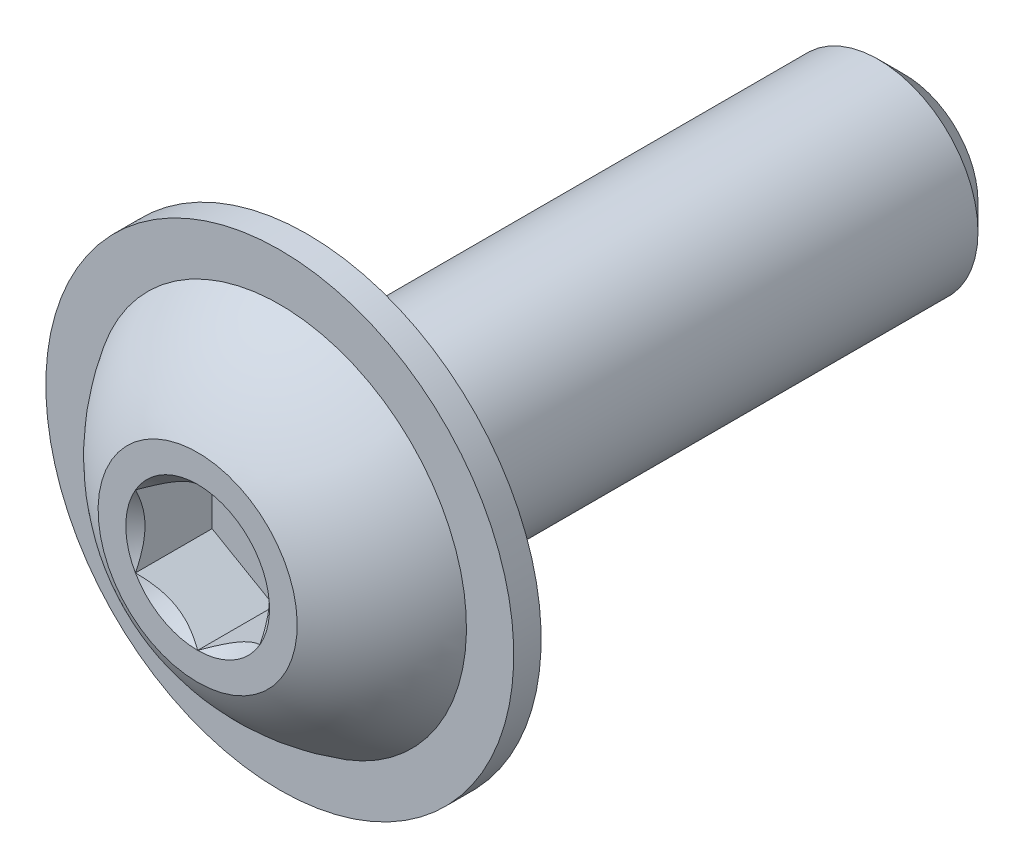
SolidWorks part; units mm, degrees
material "Alloy Steel"
ref_plane "Front" through (0, 0, 0) normal (0, 0, 1) x (1, 0, 0)
ref_plane "Top" through (0, 0, 0) normal (0, 1, 0) x (1, 0, 0)
ref_plane "Right" through (0, 0, 0) normal (1, 0, 0) x (0, 0, -1)
sketch "Sketch1" plane through (0, 0, 0) normal (1, 0, 0) x (0, 0, -1)
  line L2 (-4.9, 2) -> (7.1, 2)
  line L3 (7.1, 2) -> (7.1, 0)
  line L4 (7.1, -2) -> (6.4, -2) construction
  line L6 (-5.45, 3.75) -> (-4.9, 3.75) construction
  line L7 (7.1, 2) -> (7.1, -2) construction
  line L8 (-7.1, 0) -> (7.1, 0) construction
  line L9 (-4.9, 3.75) -> (-4.9, -3.75) construction
  line L11 (-4.9, 2) -> (-4.9, 0)
  line L13 (-7.1, 1.25) -> (-7.1, -1.25) construction
  line L14 (-7.1, 1.25) -> (-7.1, 2) construction
  line L15 (-5.45, 3.75) -> (-5.45, 4.7) construction
  line L16 (-5.45, 4.7) -> (-4.9, 4.7) construction
  line L17 (-4.9, 4.7) -> (-4.9, 3.75) construction
  line L18 (-4.9, 4.7) -> (-4.9, -4.7) construction
  arc A3 (-7.1, 2) -> (-5.45, 3.75) centre (-3.2258, 0) cw construction
  point P16 (4.65, -2)
  point P24 (0, 0)
  dimension "Thread OD" = 4
  dimension "D1" = 0.55
  dimension "Head Height" = 2.2
  dimension "Head Diameter" = 7.5
  dimension "Length" = 12
  dimension "Drive Size" = 2.5
  dimension "Flange Diameter" = 9.4
  dimension "D2" = 2.45
  dimension "Thread Pitch" = 0.7
sketch "Sketch13" plane through (0, 0, 0) normal (1, 0, 0) x (0, 0, -1)
  line L1 (-4.9, 2) -> (7.1, 2)
  line L2 (-4.9, 2) -> (-4.9, 0)
  line L3 (-4.9, 0) -> (7.1, 0)
  line L4 (7.1, 2) -> (7.1, 0)
revolve "Revolve1" add sketch "Sketch13" angle 360 about L8
chamfer "Chamfer1" distance 0.525 angle 45 1 edges at (2, 0, -7.1)
sketch "Sketch7" plane through (0, 0, 0) normal (1, 0, 0) x (0, 0, -1)
  line L0 (-4.9, 3.75) -> (-4.9, -3.75) construction
  line L1 (-4.9, 3.75) -> (-4.9, 0)
  line L2 (-5.45, 3.75) -> (-5.45, 4.7)
  line L3 (-5.45, 4.7) -> (-4.9, 4.7)
  line L4 (-4.9, 4.7) -> (-4.9, 3.75)
  line L6 (-5.45, 3.75) -> (-4.9, 3.75) construction
  line L8 (-7.1, 0) -> (7.1, 0) construction
  line L12 (-5.45, 3.75) -> (-4.9, 3.75) construction
  line L13 (-7.1, 0) -> (-4.9, 0)
  line L14 (-7.1, 1.25) -> (-7.1, -1.25) construction
  line L16 (-7.1, 2) -> (-7.1, 0)
  arc A2 (-5.45, 3.75) -> (-7.1, 2) centre (-3.2258, 0) ccw construction
  arc A3 (-5.45, 3.75) -> (-7.1, 2) centre (-3.2258, 0) ccw
revolve "Revolve2" add sketch "Sketch7" angle 360 mid plane about L13
sketch "Sketch5" plane through (0, 0, 7.1) normal (0, 0, 1) x (1, 0, 0)
  line L1 (1.25, -0.7217) -> (1.25, 0.7217)
  line L2 (1.25, 0.7217) -> (0, 1.4434)
  line L3 (0, 1.4434) -> (-1.25, 0.7217)
  line L4 (-1.25, 0.7217) -> (-1.25, -0.7217)
  line L5 (-1.25, -0.7217) -> (0, -1.4434)
  line L6 (0, -1.4434) -> (1.25, -0.7217)
  circle A0 centre (0, 0) radius 1.25 construction
extrude "Cut-Extrude2" cut sketch "Sketch5" against normal blind 1.54
sketch "Sketch6" plane through (0, 0, 7.1) normal (0, 0, 1) x (1, 0, 0)
  circle A0 centre (0, 0) radius 1.4434
extrude "Cut-Extrude3" cut sketch "Sketch6" against normal blind 1.54 draft 45
split "Split1" [suppressed] bodies to split 113
sketch "Sketch14" [suppressed] plane through (0, 0, -7.1) normal (0, 0, -1) x (-1, 0, 0)
  circle A0 centre (0, 0) radius 2 construction
  circle A1 centre (0, 0) radius 2
curve "Helix/Spiral1" [suppressed] pitch 0.7 height 12.7 turns 18.1429
sketch "Sketch16" [suppressed] plane through (0, 0, 0) normal (1, 0, 0) x (0, 0, -1)
  line L0 (7.7562, 2.0758) -> (7.0563, 2.0758) construction
  line L1 (7.0563, 2.0758) -> (7.4062, 1.4696) construction
  line L2 (7.4062, 1.4696) -> (7.7562, 2.0758) construction
  line L3 (7.7125, 2) -> (7.1, 2) construction
  line L4 (7.4062, 2.0758) -> (7.4062, 2) construction
  line L5 (7.7344, 2.0379) -> (7.0781, 2.0379) construction
  line L6 (7.45, 1.5453) -> (7.3625, 1.5453) construction
  line L7 (7.4062, 1.5453) -> (7.4062, 1.4696) construction
  line L8 (7.3625, 1.5453) -> (7.0781, 2.0379)
  line L9 (7.0781, 2.0379) -> (7.7344, 2.0379)
  line L10 (7.7344, 2.0379) -> (7.45, 1.5453)
  line L11 (7.45, 1.5453) -> (7.3625, 1.5453)
  point P11 (7.4062, 2.0379)
  dimension "D1" = 0.7
  dimension "D2" = 0.0875
sweep "Cut-Sweep1" [suppressed] cut profiles "Sketch16" path "Helix/Spiral1"
sketch "Sketch17" [suppressed] plane through (0, 0, 4.9) normal (0, 0, -1) x (-1, 0, 0)
  circle A1 centre (0, 0) radius 2
  circle A2 centre (0, 0) radius 2
  dimension "D1" = 0
extrude "Boss-Extrude1" [suppressed] add sketch "Sketch17" along normal up to next draft 20
equation "\"D3@Helix/Spiral1\" = \"Length@Sketch1\" + \"D4@Helix/Spiral1\""
equation "\"D1@Chamfer1\" = \"D4@Helix/Spiral1\" * .75"
equation "\"D1@Cut-Extrude2\" = \"Head Height@Sketch1\" * .7"
equation "\"D1@Sketch1\" = \"Head Height@Sketch1\" * .25"
equation "\"D1@Cut-Extrude3\" = \"D1@Cut-Extrude2\""
equation "\"D2@Sketch1\"=\"D4@Helix/Spiral1\"*3.5"
equation "\"D4@Helix/Spiral1\"=\"Thread Pitch@Sketch1\""
equation "\"D1@Sketch16\"=\"Thread Pitch@Sketch1\""
equation "\"D2@Sketch16\"=\"D1@Sketch16\"/8"
